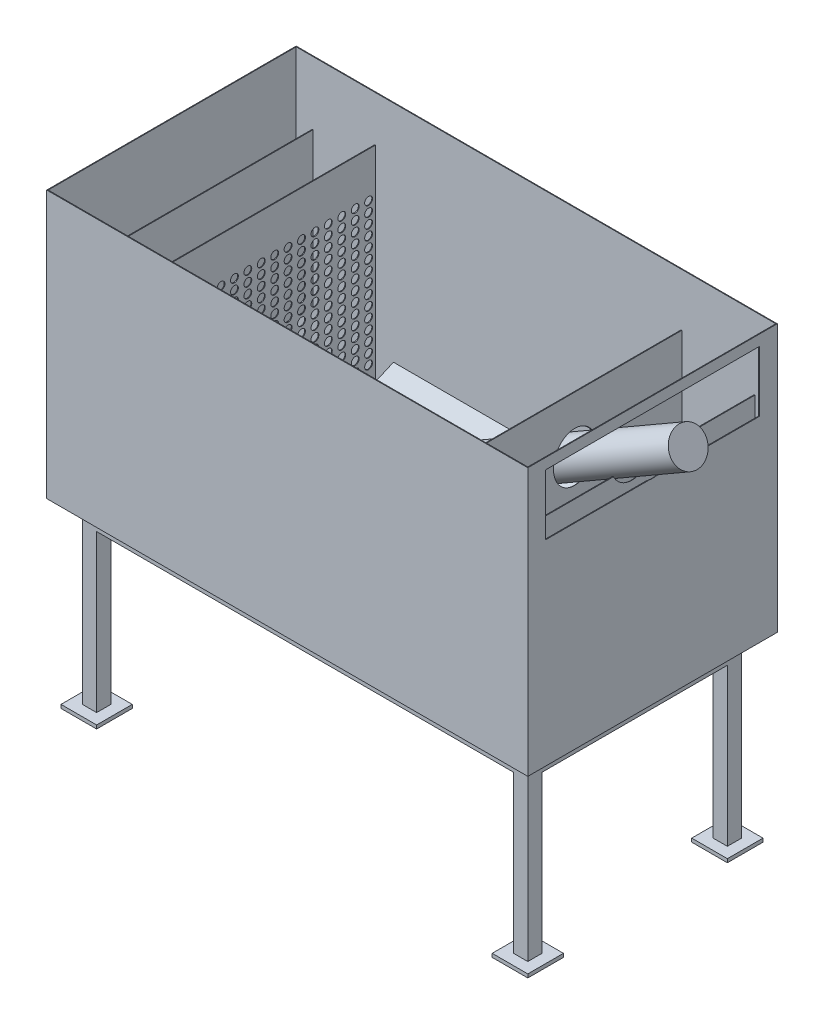
SolidWorks part; units mm, degrees
ref_plane "Спереди" through (0, 0, 0) normal (0, 0, 1) x (1, 0, 0)
ref_plane "Сверху" through (0, 0, 0) normal (0, 1, 0) x (1, 0, 0)
ref_plane "Справа" through (0, 0, 0) normal (1, 0, 0) x (0, 0, -1)
sketch "MASTER_FOOTPRINT" plane through (0, 0, 0) normal (0, 1, 0) x (1, 0, 0)
  line L1 (0, 0) -> (1350, 0)
  line L2 (0, 0) -> (0, 700)
  line L3 (0, 700) -> (1350, 700)
  line L4 (1350, 0) -> (1350, 700)
  dimension "D1" = 1350
  dimension "D2" = 700
extrude "BATH_BASE_PLATE" add sketch "MASTER_FOOTPRINT" along normal blind 750
shell "BATH_SHELL_2MM" thickness 2 removed face at (675, 750, -350)
sketch "Эскиз1" plane through (0, 0, 0) normal (1, 0, 0) x (0, 0, -1)
  circle A0 centre (350, 420) radius 50
extrude "INLET_D100_OPENING" cut sketch "Эскиз1" along normal blind 10
sketch "Эскиз2" plane through (0, 0, 0) normal (1, 0, 0) x (0, 0, -1)
  line L1 (80, 220) -> (620, 220)
  line L2 (80, 220) -> (80, 650)
  line L3 (80, 650) -> (620, 650)
  line L4 (620, 220) -> (620, 650)
extrude "INLET_IMPACT_BAFFLE" add sketch "Эскиз2" along normal blind 2 from offset 125 separate body
sketch "Эскиз3" plane through (0, 0, 0) normal (1, 0, 0) x (0, 0, -1)
  line L1 (30, 2) -> (670, 2)
  line L2 (30, 2) -> (30, 650)
  line L3 (30, 650) -> (670, 650)
  line L4 (670, 2) -> (670, 650)
  circle A0 centre (48.8235, 125) radius 11
  circle A1 centre (48.8235, 153.5) radius 11
  circle A2 centre (48.8235, 182) radius 11
  circle A3 centre (48.8235, 210.5) radius 11
  circle A4 centre (48.8235, 239) radius 11
  circle A5 centre (48.8235, 267.5) radius 11
  circle A6 centre (48.8235, 296) radius 11
  circle A7 centre (48.8235, 324.5) radius 11
  circle A8 centre (48.8235, 353) radius 11
  circle A9 centre (48.8235, 381.5) radius 11
  circle A10 centre (48.8235, 410) radius 11
  circle A11 centre (48.8235, 438.5) radius 11
  circle A12 centre (48.8235, 467) radius 11
  circle A13 centre (48.8235, 495.5) radius 11
  circle A14 centre (48.8235, 524) radius 11
  circle A15 centre (86.4706, 125) radius 11
  circle A16 centre (86.4706, 153.5) radius 11
  circle A17 centre (86.4706, 182) radius 11
  circle A18 centre (86.4706, 210.5) radius 11
  circle A19 centre (86.4706, 239) radius 11
  circle A20 centre (86.4706, 267.5) radius 11
  circle A21 centre (86.4706, 296) radius 11
  circle A22 centre (86.4706, 324.5) radius 11
  circle A23 centre (86.4706, 353) radius 11
  circle A24 centre (86.4706, 381.5) radius 11
  circle A25 centre (86.4706, 410) radius 11
  circle A26 centre (86.4706, 438.5) radius 11
  circle A27 centre (86.4706, 467) radius 11
  circle A28 centre (86.4706, 495.5) radius 11
  circle A29 centre (86.4706, 524) radius 11
  circle A30 centre (124.1176, 125) radius 11
  circle A31 centre (124.1176, 153.5) radius 11
  circle A32 centre (124.1176, 182) radius 11
  circle A33 centre (124.1176, 210.5) radius 11
  circle A34 centre (124.1176, 239) radius 11
  circle A35 centre (124.1176, 267.5) radius 11
  circle A36 centre (124.1176, 296) radius 11
  circle A37 centre (124.1176, 324.5) radius 11
  circle A38 centre (124.1176, 353) radius 11
  circle A39 centre (124.1176, 381.5) radius 11
  circle A40 centre (124.1176, 410) radius 11
  circle A41 centre (124.1176, 438.5) radius 11
  circle A42 centre (124.1176, 467) radius 11
  circle A43 centre (124.1176, 495.5) radius 11
  circle A44 centre (124.1176, 524) radius 11
  circle A45 centre (161.7647, 125) radius 11
  circle A46 centre (161.7647, 153.5) radius 11
  circle A47 centre (161.7647, 182) radius 11
  circle A48 centre (161.7647, 210.5) radius 11
  circle A49 centre (161.7647, 239) radius 11
  circle A50 centre (161.7647, 267.5) radius 11
  circle A51 centre (161.7647, 296) radius 11
  circle A52 centre (161.7647, 324.5) radius 11
  circle A53 centre (161.7647, 353) radius 11
  circle A54 centre (161.7647, 381.5) radius 11
  circle A55 centre (161.7647, 410) radius 11
  circle A56 centre (161.7647, 438.5) radius 11
  circle A57 centre (161.7647, 467) radius 11
  circle A58 centre (161.7647, 495.5) radius 11
  circle A59 centre (161.7647, 524) radius 11
  circle A60 centre (199.4118, 125) radius 11
  circle A61 centre (199.4118, 153.5) radius 11
  circle A62 centre (199.4118, 182) radius 11
  circle A63 centre (199.4118, 210.5) radius 11
  circle A64 centre (199.4118, 239) radius 11
  circle A65 centre (199.4118, 267.5) radius 11
  circle A66 centre (199.4118, 296) radius 11
  circle A67 centre (199.4118, 324.5) radius 11
  circle A68 centre (199.4118, 353) radius 11
  circle A69 centre (199.4118, 381.5) radius 11
  circle A70 centre (199.4118, 410) radius 11
  circle A71 centre (199.4118, 438.5) radius 11
  circle A72 centre (199.4118, 467) radius 11
  circle A73 centre (199.4118, 495.5) radius 11
  circle A74 centre (199.4118, 524) radius 11
  circle A75 centre (237.0588, 125) radius 11
  circle A76 centre (237.0588, 153.5) radius 11
  circle A77 centre (237.0588, 182) radius 11
  circle A78 centre (237.0588, 210.5) radius 11
  circle A79 centre (237.0588, 239) radius 11
  circle A80 centre (237.0588, 267.5) radius 11
  circle A81 centre (237.0588, 296) radius 11
  circle A82 centre (237.0588, 324.5) radius 11
  circle A83 centre (237.0588, 353) radius 11
  circle A84 centre (237.0588, 381.5) radius 11
  circle A85 centre (237.0588, 410) radius 11
  circle A86 centre (237.0588, 438.5) radius 11
  circle A87 centre (237.0588, 467) radius 11
  circle A88 centre (237.0588, 495.5) radius 11
  circle A89 centre (237.0588, 524) radius 11
  circle A90 centre (274.7059, 125) radius 11
  circle A91 centre (274.7059, 153.5) radius 11
  circle A92 centre (274.7059, 182) radius 11
  circle A93 centre (274.7059, 210.5) radius 11
  circle A94 centre (274.7059, 239) radius 11
  circle A95 centre (274.7059, 267.5) radius 11
  circle A96 centre (274.7059, 296) radius 11
  circle A97 centre (274.7059, 324.5) radius 11
  circle A98 centre (274.7059, 353) radius 11
  circle A99 centre (274.7059, 381.5) radius 11
  circle A100 centre (274.7059, 410) radius 11
  circle A101 centre (274.7059, 438.5) radius 11
  circle A102 centre (274.7059, 467) radius 11
  circle A103 centre (274.7059, 495.5) radius 11
  circle A104 centre (274.7059, 524) radius 11
  circle A105 centre (312.3529, 125) radius 11
  circle A106 centre (312.3529, 153.5) radius 11
  circle A107 centre (312.3529, 182) radius 11
  circle A108 centre (312.3529, 210.5) radius 11
  circle A109 centre (312.3529, 239) radius 11
  circle A110 centre (312.3529, 267.5) radius 11
  circle A111 centre (312.3529, 296) radius 11
  circle A112 centre (312.3529, 324.5) radius 11
  circle A113 centre (312.3529, 353) radius 11
  circle A114 centre (312.3529, 381.5) radius 11
  circle A115 centre (312.3529, 410) radius 11
  circle A116 centre (312.3529, 438.5) radius 11
  circle A117 centre (312.3529, 467) radius 11
  circle A118 centre (312.3529, 495.5) radius 11
  circle A119 centre (312.3529, 524) radius 11
  circle A120 centre (350, 125) radius 11
  circle A121 centre (350, 153.5) radius 11
  circle A122 centre (350, 182) radius 11
  circle A123 centre (350, 210.5) radius 11
  circle A124 centre (350, 239) radius 11
  circle A125 centre (350, 267.5) radius 11
  circle A126 centre (350, 296) radius 11
  circle A127 centre (350, 324.5) radius 11
  circle A128 centre (350, 353) radius 11
  circle A129 centre (350, 381.5) radius 11
  circle A130 centre (350, 410) radius 11
  circle A131 centre (350, 438.5) radius 11
  circle A132 centre (350, 467) radius 11
  circle A133 centre (350, 495.5) radius 11
  circle A134 centre (350, 524) radius 11
  circle A135 centre (387.6471, 125) radius 11
  circle A136 centre (387.6471, 153.5) radius 11
  circle A137 centre (387.6471, 182) radius 11
  circle A138 centre (387.6471, 210.5) radius 11
  circle A139 centre (387.6471, 239) radius 11
  circle A140 centre (387.6471, 267.5) radius 11
  circle A141 centre (387.6471, 296) radius 11
  circle A142 centre (387.6471, 324.5) radius 11
  circle A143 centre (387.6471, 353) radius 11
  circle A144 centre (387.6471, 381.5) radius 11
  circle A145 centre (387.6471, 410) radius 11
  circle A146 centre (387.6471, 438.5) radius 11
  circle A147 centre (387.6471, 467) radius 11
  circle A148 centre (387.6471, 495.5) radius 11
  circle A149 centre (387.6471, 524) radius 11
  circle A150 centre (425.2941, 125) radius 11
  circle A151 centre (425.2941, 153.5) radius 11
  circle A152 centre (425.2941, 182) radius 11
  circle A153 centre (425.2941, 210.5) radius 11
  circle A154 centre (425.2941, 239) radius 11
  circle A155 centre (425.2941, 267.5) radius 11
  circle A156 centre (425.2941, 296) radius 11
  circle A157 centre (425.2941, 324.5) radius 11
  circle A158 centre (425.2941, 353) radius 11
  circle A159 centre (425.2941, 381.5) radius 11
  circle A160 centre (425.2941, 410) radius 11
  circle A161 centre (425.2941, 438.5) radius 11
  circle A162 centre (425.2941, 467) radius 11
  circle A163 centre (425.2941, 495.5) radius 11
  circle A164 centre (425.2941, 524) radius 11
  circle A165 centre (462.9412, 125) radius 11
  circle A166 centre (462.9412, 153.5) radius 11
  circle A167 centre (462.9412, 182) radius 11
  circle A168 centre (462.9412, 210.5) radius 11
  circle A169 centre (462.9412, 239) radius 11
  circle A170 centre (462.9412, 267.5) radius 11
  circle A171 centre (462.9412, 296) radius 11
  circle A172 centre (462.9412, 324.5) radius 11
  circle A173 centre (462.9412, 353) radius 11
  circle A174 centre (462.9412, 381.5) radius 11
  circle A175 centre (462.9412, 410) radius 11
  circle A176 centre (462.9412, 438.5) radius 11
  circle A177 centre (462.9412, 467) radius 11
  circle A178 centre (462.9412, 495.5) radius 11
  circle A179 centre (462.9412, 524) radius 11
  circle A180 centre (500.5882, 125) radius 11
  circle A181 centre (500.5882, 153.5) radius 11
  circle A182 centre (500.5882, 182) radius 11
  circle A183 centre (500.5882, 210.5) radius 11
  circle A184 centre (500.5882, 239) radius 11
  circle A185 centre (500.5882, 267.5) radius 11
  circle A186 centre (500.5882, 296) radius 11
  circle A187 centre (500.5882, 324.5) radius 11
  circle A188 centre (500.5882, 353) radius 11
  circle A189 centre (500.5882, 381.5) radius 11
  circle A190 centre (500.5882, 410) radius 11
  circle A191 centre (500.5882, 438.5) radius 11
  circle A192 centre (500.5882, 467) radius 11
  circle A193 centre (500.5882, 495.5) radius 11
  circle A194 centre (500.5882, 524) radius 11
  circle A195 centre (538.2353, 125) radius 11
  circle A196 centre (538.2353, 153.5) radius 11
  circle A197 centre (538.2353, 182) radius 11
  circle A198 centre (538.2353, 210.5) radius 11
  circle A199 centre (538.2353, 239) radius 11
  circle A200 centre (538.2353, 267.5) radius 11
  circle A201 centre (538.2353, 296) radius 11
  circle A202 centre (538.2353, 324.5) radius 11
  circle A203 centre (538.2353, 353) radius 11
  circle A204 centre (538.2353, 381.5) radius 11
  circle A205 centre (538.2353, 410) radius 11
  circle A206 centre (538.2353, 438.5) radius 11
  circle A207 centre (538.2353, 467) radius 11
  circle A208 centre (538.2353, 495.5) radius 11
  circle A209 centre (538.2353, 524) radius 11
  circle A210 centre (575.8824, 125) radius 11
  circle A211 centre (575.8824, 153.5) radius 11
  circle A212 centre (575.8824, 182) radius 11
  circle A213 centre (575.8824, 210.5) radius 11
  circle A214 centre (575.8824, 239) radius 11
  circle A215 centre (575.8824, 267.5) radius 11
  circle A216 centre (575.8824, 296) radius 11
  circle A217 centre (575.8824, 324.5) radius 11
  circle A218 centre (575.8824, 353) radius 11
  circle A219 centre (575.8824, 381.5) radius 11
  circle A220 centre (575.8824, 410) radius 11
  circle A221 centre (575.8824, 438.5) radius 11
  circle A222 centre (575.8824, 467) radius 11
  circle A223 centre (575.8824, 495.5) radius 11
  circle A224 centre (575.8824, 524) radius 11
  circle A225 centre (613.5294, 125) radius 11
  circle A226 centre (613.5294, 153.5) radius 11
  circle A227 centre (613.5294, 182) radius 11
  circle A228 centre (613.5294, 210.5) radius 11
  circle A229 centre (613.5294, 239) radius 11
  circle A230 centre (613.5294, 267.5) radius 11
  circle A231 centre (613.5294, 296) radius 11
  circle A232 centre (613.5294, 324.5) radius 11
  circle A233 centre (613.5294, 353) radius 11
  circle A234 centre (613.5294, 381.5) radius 11
  circle A235 centre (613.5294, 410) radius 11
  circle A236 centre (613.5294, 438.5) radius 11
  circle A237 centre (613.5294, 467) radius 11
  circle A238 centre (613.5294, 495.5) radius 11
  circle A239 centre (613.5294, 524) radius 11
  circle A240 centre (651.1765, 125) radius 11
  circle A241 centre (651.1765, 153.5) radius 11
  circle A242 centre (651.1765, 182) radius 11
  circle A243 centre (651.1765, 210.5) radius 11
  circle A244 centre (651.1765, 239) radius 11
  circle A245 centre (651.1765, 267.5) radius 11
  circle A246 centre (651.1765, 296) radius 11
  circle A247 centre (651.1765, 324.5) radius 11
  circle A248 centre (651.1765, 353) radius 11
  circle A249 centre (651.1765, 381.5) radius 11
  circle A250 centre (651.1765, 410) radius 11
  circle A251 centre (651.1765, 438.5) radius 11
  circle A252 centre (651.1765, 467) radius 11
  circle A253 centre (651.1765, 495.5) radius 11
  circle A254 centre (651.1765, 524) radius 11
extrude "DISTRIBUTOR_D22" add sketch "Эскиз3" along normal blind 2 from offset 250 separate body
sketch "Эскиз4" plane through (0, 0, 0) normal (1, 0, 0) x (0, 0, -1)
  line L1 (50, 320) -> (650, 320)
  line L2 (50, 320) -> (50, 650)
  line L3 (50, 650) -> (650, 650)
  line L4 (650, 320) -> (650, 650)
extrude "OUTLET_SUBMERGED_BAFFLE" add sketch "Эскиз4" along normal blind 2 from offset 1130 separate body
sketch "Эскиз5" plane through (0, 0, 0) normal (1, 0, 0) x (0, 0, -1)
  line L1 (5, 2) -> (695, 2)
  line L2 (5, 2) -> (5, 550)
  line L3 (5, 550) -> (695, 550)
  line L4 (695, 2) -> (695, 550)
extrude "OVERFLOW_WEIR_Z550" add sketch "Эскиз5" along normal blind 2 from offset 1290 separate body
sketch "Эскиз6" plane through (0, 0, 0) normal (1, 0, 0) x (0, 0, -1)
  line L1 (50, 550) -> (650, 550)
  line L2 (50, 550) -> (50, 720)
  line L3 (50, 720) -> (650, 720)
  line L4 (650, 550) -> (650, 720)
extrude "OUTLET_WEIR_SLOT_W600" cut sketch "Эскиз6" along normal blind 10 from offset 1345
sketch "Эскиз7" plane through (0, 0, 0) normal (1, 0, 0) x (0, 0, -1)
  line L0 (2, -1) -> (2, 120)
  line L1 (2, 120) -> (280, -1)
  line L2 (280, -1) -> (2, -1)
  line L3 (698, -1) -> (698, 120)
  line L4 (698, 120) -> (420, -1)
  line L5 (420, -1) -> (698, -1)
extrude "SLOPED_SEDIMENT_FLOOR" add sketch "Эскиз7" along normal blind 825 from offset 275
sketch3d "SCREW_AXIS_30DEG_REFERENCE"
  line L0 (400, 70, -350) -> (1450, 676.2178, -350)
sketch "Эскиз8" plane through (0, 0, 0) normal (0, 1, 0) x (1, 0, 0)
  line L1 (50, 50) -> (90, 50)
  line L2 (50, 50) -> (50, 90)
  line L3 (50, 90) -> (90, 90)
  line L4 (90, 50) -> (90, 90)
  line L6 (50, 610) -> (90, 610)
  line L7 (50, 610) -> (50, 650)
  line L8 (50, 650) -> (90, 650)
  line L9 (90, 610) -> (90, 650)
  line L11 (1260, 50) -> (1300, 50)
  line L12 (1260, 50) -> (1260, 90)
  line L13 (1260, 90) -> (1300, 90)
  line L14 (1300, 50) -> (1300, 90)
  line L16 (1260, 610) -> (1300, 610)
  line L17 (1260, 610) -> (1260, 650)
  line L18 (1260, 650) -> (1300, 650)
  line L19 (1300, 610) -> (1300, 650)
extrude "FRAME_LEGS_40X40_H500" add sketch "Эскиз8" against normal blind 500
sketch "Эскиз9" plane through (0, 0, 0) normal (0, 1, 0) x (1, 0, 0)
  line L1 (50, 50) -> (1300, 50)
  line L2 (50, 50) -> (50, 90)
  line L3 (50, 90) -> (1300, 90)
  line L4 (1300, 50) -> (1300, 90)
  line L6 (50, 610) -> (1300, 610)
  line L7 (50, 610) -> (50, 650)
  line L8 (50, 650) -> (1300, 650)
  line L9 (1300, 610) -> (1300, 650)
extrude "FRAME_LONGITUDINAL_RAILS" add sketch "Эскиз9" against normal blind 40 from offset 20 offset against normal yes
sketch "Эскиз10" plane through (0, 0, 0) normal (0, 1, 0) x (1, 0, 0)
  line L1 (50, 90) -> (90, 90)
  line L2 (50, 90) -> (50, 610)
  line L3 (50, 610) -> (90, 610)
  line L4 (90, 90) -> (90, 610)
  line L6 (1260, 90) -> (1300, 90)
  line L7 (1260, 90) -> (1260, 610)
  line L8 (1260, 610) -> (1300, 610)
  line L9 (1300, 90) -> (1300, 610)
extrude "FRAME_TRANSVERSE_RAILS" add sketch "Эскиз10" against normal blind 40 from offset 20 offset against normal yes
sketch "Эскиз11" plane through (0, 0, 0) normal (0, 1, 0) x (1, 0, 0)
  line L1 (20, 20) -> (120, 20)
  line L2 (20, 20) -> (20, 120)
  line L3 (20, 120) -> (120, 120)
  line L4 (120, 20) -> (120, 120)
  line L6 (20, 580) -> (120, 580)
  line L7 (20, 580) -> (20, 680)
  line L8 (20, 680) -> (120, 680)
  line L9 (120, 580) -> (120, 680)
  line L11 (1230, 20) -> (1330, 20)
  line L12 (1230, 20) -> (1230, 120)
  line L13 (1230, 120) -> (1330, 120)
  line L14 (1330, 20) -> (1330, 120)
  line L16 (1230, 580) -> (1330, 580)
  line L17 (1230, 580) -> (1230, 680)
  line L18 (1230, 680) -> (1330, 680)
  line L19 (1330, 580) -> (1330, 680)
extrude "FRAME_FOOT_PADS_100X100" add sketch "Эскиз11" against normal blind 10 from offset 500 offset against normal yes
sweep "SEALED_SCREW_PASSAGE_D120" cut path "SCREW_AXIS_30DEG_REFERENCE" circular profile diameter 120 parameters "D3"=120
sweep "SCREW_OUTER_ENVELOPE_D100" add path "SCREW_AXIS_30DEG_REFERENCE<2>" circular profile diameter 100 parameters "D3"=100
sketch3d "SCREW_AXIS_30DEG_REFERENCE<2>" same geometry as "SCREW_AXIS_30DEG_REFERENCE"
equation "\"AI_Q_Peak\"= 0.006"
equation "\"AI_B_Bath\"= 700"
equation "\"AI_L_Settle\"= 900"
equation "\"AI_L_Inlet\"= 250"
equation "\"AI_L_Outlet\"= 200"
equation "\"AI_L_Bath\"= 1350"
equation "\"AI_H_Water\"= 550"
equation "\"AI_H_Freeboard\"= 200"
equation "\"AI_H_Bath\"= 750"
equation "\"AI_Shell_Thickness\"= 2"
equation "\"AI_Inlet_DN\"= 100"
equation "\"AI_Weir_Width\"= 600"
equation "\"AI_Inlet_Baffle_Offset\"= 125"
equation "\"AI_Distributor_Open_Area\"= 0.28"
equation "\"AI_Distributor_Hole_Dia\"= 22"
equation "\"AI_Distributor_Blind_Zone\"= 110"
equation "\"AI_Outlet_Baffle_Depth\"= 250"
equation "\"AI_Screw_Diameter\"= 100"
equation "\"AI_Screw_Pitch\"= 100"
equation "\"AI_Screw_Angle\"= 30"
equation "\"AI_Screw_Rpm\"= 15"
equation "\"AI_Screw_Clearance\"= 5"
equation "\"AI_Liner_Thickness\"= 5"
equation "\"AI_Discharge_Height\"= 650"
equation "\"AI_Frame_Height\"= 500"
equation "\"D1@MASTER_FOOTPRINT\" = \"AI_L_Bath\""
equation "\"D2@MASTER_FOOTPRINT\" = \"AI_B_Bath\""
equation "\"D1@BATH_BASE_PLATE\" = \"AI_H_Bath\""
